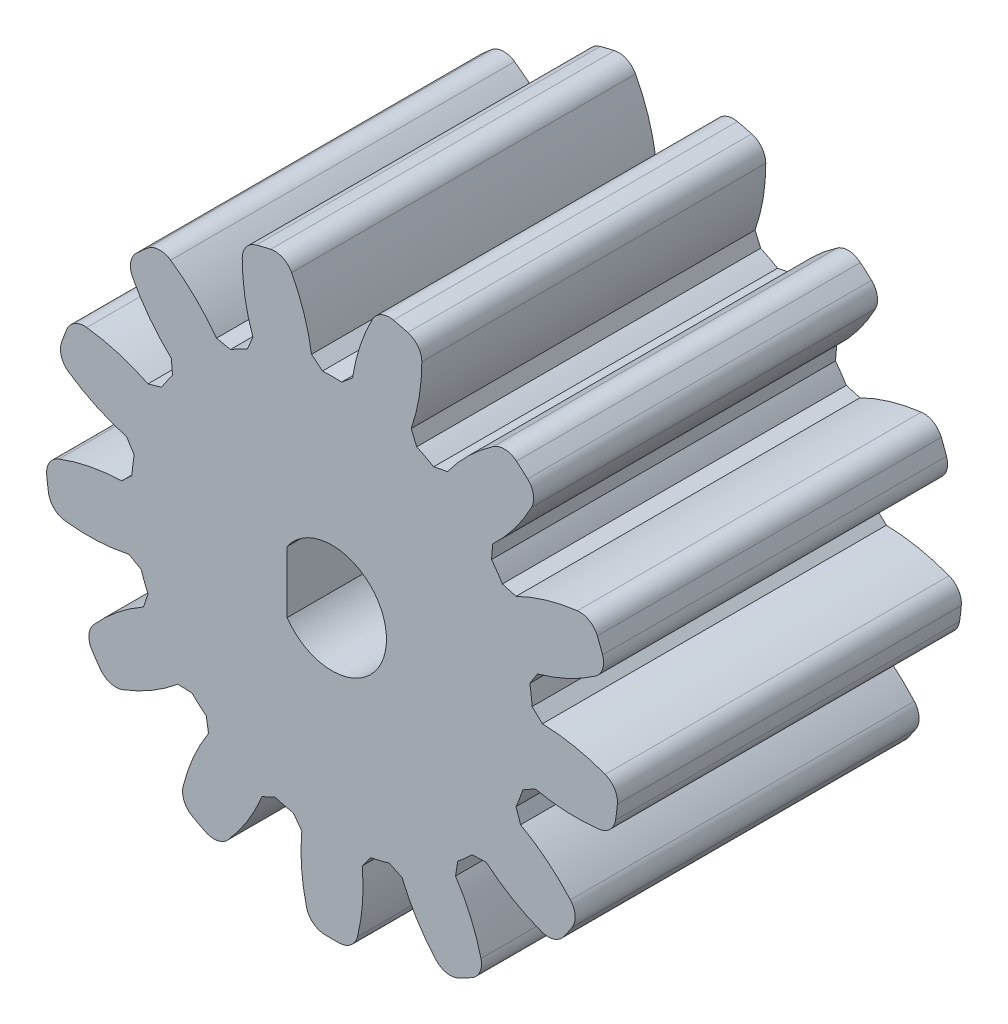
SolidWorks part; units mm, degrees
ref_plane "Front Plane" through (0, 0, 0) normal (0, 0, 1) x (1, 0, 0)
ref_plane "Top Plane" through (0, 0, 0) normal (0, 1, 0) x (1, 0, 0)
ref_plane "Right Plane" through (0, 0, 0) normal (1, 0, 0) x (0, 0, -1)
sketch "Sketch1" plane through (0, 0, 0) normal (0, 0, 1) x (1, 0, 0)
  circle A0 centre (0, 0) radius 13 construction
  circle A1 centre (0, 0) radius 15
  dimension "D1" = 26
  dimension "D2" = 30
extrude "Boss-Extrude1" add sketch "Sketch1" along normal mid plane 18
sketch "Sketch2" plane through (0, 0, 0) normal (0, 0, 1) x (1, 0, 0)
  line L0 (0, 15) -> (0, 0) construction
  line L1 (2.4887, 14.7921) -> (2.4887, 15.174)
  line L2 (0, 0) -> (3.5897, 14.5641) construction
  line L3 (-1.0111, 10.4512) -> (0, 0) construction
  line L4 (-1.567, 12.9052) -> (1.567, 12.9052) construction
  line L5 (1.567, 12.9052) -> (4.6099, 12.1552) construction
  line L6 (-2.2667, 14.8277) -> (0, 8.6) construction
  line L7 (2.4887, 15.174) -> (-2.6144, 15.174)
  line L8 (-2.6144, 15.174) -> (-2.4887, 14.7921)
  circle A1 centre (0, 0) radius 11 construction
  circle A2 centre (0, 0) radius 15 construction
  arc A3 (-2.4887, 14.7921) -> (-1.0111, 10.4512) centre (-10.9515, 9.4895) cw
  circle A4 centre (0, 0) radius 15 construction
  arc A5 (2.4887, 14.7921) -> (1.0111, 10.4512) centre (10.9515, 9.4895) ccw
  circle A6 centre (0, 0) radius 13 construction
  arc A7 (1.0111, 10.4512) -> (-1.0111, 10.4512) centre (0, 0) ccw
  dimension "D2" = 4
  dimension "D4" = 20
extrude "Cut-Extrude1" cut sketch "Sketch2" against normal through all both and the other way through all
pattern_circular "CirPattern1" count 13 over 360 about axis through (0, 0, 9) along (0, 0, -1) of "Cut-Extrude1"
fillet "Fillet1" radius 1 26 edges at (-12.9484, -7.5723, 0) (-11.6718, -9.4217, 0) (-7.9462, -12.7224, 0) (-5.9564, -13.7667, 0) (-1.1236, -14.9579, 0) (1.1236, -14.9579, 0) (5.9564, -13.7667, 0) (7.9462, -12.7224, 0) (11.6718, -9.4217, 0) (12.9484, -7.5723, 0) (14.7134, -2.9184, 0) (14.9842, -0.6876, 0) (14.3843, 4.2536, 0) (13.5874, 6.3547, 0) (10.7599, 10.451, 0) (9.0779, 11.9412, 0) (4.6706, 14.2543, 0) (2.4887, 14.7921, 0) (-2.4887, 14.7921, 0) (-4.6706, 14.2543, 0) (-9.0779, 11.9412, 0) (-10.7599, 10.451, 0) (-13.5874, 6.3547, 0) (-14.3843, 4.2536, 0) (-14.9842, -0.6876, 0) (-14.7134, -2.9184, 0)
chamfer "Chamfer1" distance 0.5 angle 45 26 edges at (-10.2531, 2.2635, 0) (-10.4969, 0.256, 0) (-10.1306, -2.7606, 0) (-9.4135, -4.6514, 0) (-7.6873, -7.1524, 0) (-6.1736, -8.4933, 0) (-3.4829, -9.9055, 0) (-1.5194, -10.3895, 0) (1.5194, -10.3895, 0) (3.4829, -9.9055, 0) (6.1736, -8.4933, 0) (7.6873, -7.1524, 0) (9.4135, -4.6514, 0) (10.1306, -2.7606, 0) (10.4969, 0.256, 0) (10.2531, 2.2635, 0) (9.1755, 5.1048, 0) (8.0268, 6.7691, 0) (5.7522, 8.7842, 0) (3.9616, 9.724, 0) (1.0111, 10.4512, 0) (-1.0111, 10.4512, 0) (-3.9616, 9.724, 0) (-5.7522, 8.7842, 0) (-8.0268, 6.7691, 0) (-9.1755, 5.1048, 0)
sketch "Sketch3" plane through (0, 0, -9) normal (0, 0, -1) x (-1, 0, 0)
  circle A0 centre (0, 0) radius 2.85
extrude "Cut-Extrude2" cut sketch "Sketch3" against normal blind 24
sketch "Sketch5" plane through (0, 0, 9) normal (0, 0, 1) x (1, 0, 0)
  line L1 (-2.35, 0) -> (-2.35, 1.6125)
  line L2 (-2.35, 0) -> (-2.35, -1.6125)
  line L3 (-2.35, -1.6125) -> (-2.85, -1.6125)
  line L4 (-2.85, -1.6125) -> (-2.85, 1.6125)
  line L5 (-2.85, 1.6125) -> (-2.35, 1.6125)
  circle A0 centre (0, 0) radius 2.85 construction
extrude "Boss-Extrude2" add sketch "Sketch5" against normal blind 8.5
fillet "Fillet3" radius 1 1 edges at (-2.35, 0, 0.5)
chamfer "Chamfer2" distance 1 angle 45 1 edges at (-2.85, 0, -9)
equation "\"Module\"= 2mm"
equation "\"Number of Teeth\"= 13"
equation "\"Pressure Angle\"= 20"
equation "\"D1@Sketch1\"=\"Module\" * \"Number of Teeth\""
equation "\"D2@Sketch1\"=( \"Number of Teeth\" + 2  )* \"Module\""
equation "\"D4@Sketch2\"= \"Pressure Angle\""
